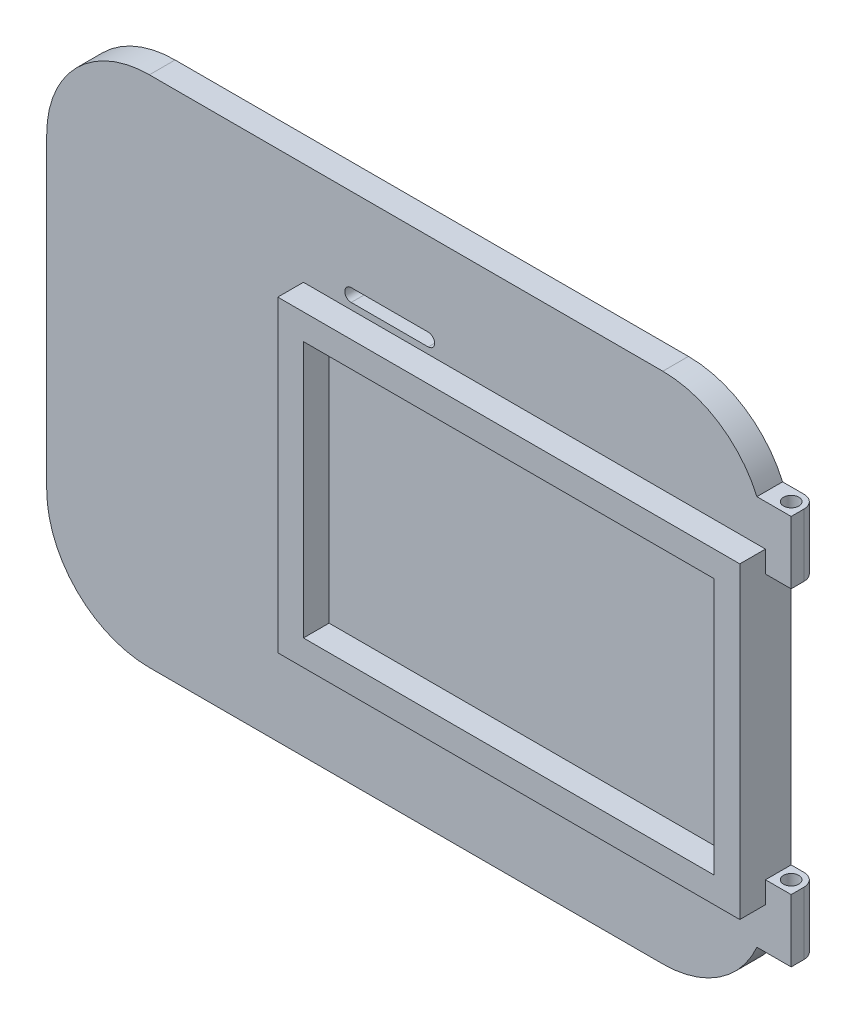
SolidWorks part; units mm, degrees
ref_plane "Front Plane" through (0, 0, 0) normal (0, 0, 1) x (1, 0, 0)
ref_plane "Top Plane" through (0, 0, 0) normal (0, 1, 0) x (1, 0, 0)
ref_plane "Right Plane" through (0, 0, 0) normal (1, 0, 0) x (0, 0, -1)
sketch "Sketch1" plane through (0, 0, 0) normal (0, 0, 1) x (1, 0, 0)
  line L0 (-63.5, 63.5) -> (63.5, 63.5)
  line L1 (63.5, -63.5) -> (-63.5, -63.5)
  line L2 (-88.9, -38.1) -> (-88.9, 38.1)
  line L3 (88.9, -38.1) -> (88.9, 38.1)
  arc A0 (-88.9, 38.1) -> (-63.5, 63.5) centre (-63.5, 38.1) cw
  arc A1 (-63.5, -63.5) -> (-88.9, -38.1) centre (-63.5, -38.1) cw
  arc A2 (63.5, -63.5) -> (88.9, -38.1) centre (63.5, -38.1) ccw
  arc A3 (88.9, 38.1) -> (63.5, 63.5) centre (63.5, 38.1) ccw
  dimension "D1" = 25.4
  dimension "D2" = 88.9
  dimension "D3" = 88.9
  dimension "D4" = 63.5
  dimension "D5" = 63.5
extrude "Boss-Extrude1" add sketch "Sketch1" against normal blind 6.35
sketch "Sketch3" plane through (0, 0, 0) normal (0, 0, 1) x (1, 0, 0)
  line L0 (63.5, 63.5) -> (88.9, 63.5) construction
  line L1 (88.9, 63.5) -> (95.25, 63.5) construction
  line L6 (95.25, 32.75) -> (95.25, 48.26)
  line L8 (95.25, 48.26) -> (86.7795, 48.26)
  line L9 (95.25, 63.5) -> (95.25, 32.75) construction
  line L10 (95.25, 32.75) -> (88.9, 32.75)
  line L11 (88.9, -38.1) -> (88.9, 38.1) construction
  line L12 (88.9, 32.75) -> (88.9, 38.1)
  arc A0 (88.9, 38.1) -> (86.7795, 48.26) centre (63.5, 38.1) ccw
  dimension "D5" = 25.4
  dimension "D1" = 25.4
  dimension "D2" = 6.35
  dimension "D3" = 30.75
  dimension "D4" = 15.24
extrude "Boss-Extrude2" add sketch "Sketch3" against normal up to surface (6.35 mm away) up to face at (0, 0, -6.35)
sketch "Sketch4" plane through (0, 48.26, 0) normal (0, 1, 0) x (1, 0, 0)
  line L0 (95.25, 3.175) -> (92.075, 3.175) construction
  line L1 (95.25, 6.35) -> (95.25, 0) construction
  circle A0 centre (92.075, 3.175) radius 1.905
  point P6 (93.98, 3.175)
  dimension "D1" = 3.81
  dimension "D2" = 1.27
extrude "Cut-Extrude2" cut sketch "Sketch4" against normal up to next
sketch "Sketch5" plane through (0, 0, 0) normal (0, 0, 1) x (1, 0, 0)
  line L0 (0, 0) -> (88.9402, 0)
mirror "Mirror1" about plane through (0, 0, 0) normal (0, 1, 0) of "Cut-Extrude2", "Boss-Extrude2"
sketch "Sketch7" plane through (0, 0, -6.35) normal (0, 0, -1) x (-1, 0, 0)
  line L0 (0, 0) -> (57.15, 0) construction
  point P4 (57.15, 0)
  dimension "D1" = 57.15
ref_plane "Plane1" through (-57.15, 0, -6.35) normal (-1, 0, 0) x (0, 0, 1)
sketch "Sketch8" plane through (-57.15, 0, -6.35) normal (-1, 0, 0) x (0, 0, 1)
  line L0 (0, 0) -> (0, 38.1) construction
  line L1 (0, 38.1) -> (0, 44.45)
  line L2 (-19.05, 25.4) -> (-19.05, -25.4)
  line L3 (0, 24.7494) -> (-24.0575, 24.7494) construction
  line L4 (-12.7, 25.4) -> (-12.7, 40.5526) construction
  line L5 (-19.05, 0) -> (-12.7, 0) construction
  line L6 (-12.7, -25.4) -> (-12.7, 25.4)
  line L7 (0, -38.1) -> (0, -44.45)
  arc A0 (0, 44.45) -> (-19.05, 25.4) centre (0, 25.4) ccw
  arc A1 (0, 38.1) -> (-12.7, 25.4) centre (0, 25.4) ccw
  arc A2 (0, -38.1) -> (-12.7, -25.4) centre (0, -25.4) cw
  arc A3 (0, -44.45) -> (-19.05, -25.4) centre (0, -25.4) cw
  dimension "D1" = 38.1
  dimension "D2" = 6.35
  dimension "D3" = 19.7006
  dimension "D4" = 12.7
extrude "Boss-Extrude3" add sketch "Sketch8" against normal blind 12.7
fillet "Fillet1" radius 6.35 1 edges at (-50.8, -44.45, -6.35)
fillet "Fillet2" radius 6.35 1 edges at (-57.15, -44.0467, -6.35)
fillet "Fillet3" radius 6.35 1 edges at (-44.45, -44.0467, -6.35)
fillet "Fillet4" radius 6.35 3 edges at (-50.8, 44.45, -6.35) (-44.45, 41.275, -6.35) (-57.15, 41.275, -6.35)
fillet "Fillet5" radius 3.175 2 edges at (95.25, -40.505, -6.35) (95.25, 40.505, -6.35)
sketch "Sketch9" plane through (0, 0, 0) normal (0, 0, 1) x (1, 0, 0)
  line L0 (88.9402, 0) -> (-88.9, 0) construction
  line L1 (-88.9, 38.1) -> (-88.9, -38.1) construction
  line L22 (82.55, 31.75) -> (-19.05, 31.75)
  line L23 (82.55, 31.75) -> (82.55, -31.75)
  line L24 (82.55, -31.75) -> (-19.05, -31.75)
  line L25 (-19.05, 31.75) -> (-19.05, -31.75)
  line L26 (-63.5, -63.5) -> (63.5, -63.5) construction
  line L27 (88.9, -32.75) -> (88.9, 32.75) construction
  line L28 (88.9, 38.1) -> (88.9, -38.1)
  line L29 (88.9, -38.1) -> (-25.4, -38.1)
  line L30 (-25.4, 38.1) -> (-25.4, -38.1)
  line L31 (88.9, 38.1) -> (-25.4, 38.1)
  dimension "D1" = 63.5
  dimension "D2" = 101.6
  dimension "D3" = 31.75
  dimension "D4" = 6.35
  dimension "D5" = 6.35
extrude "Boss-Extrude4" add sketch "Sketch9" along normal blind 6.35
sketch "Sketch10" plane through (0, 0, 0) normal (0, 0, 1) x (1, 0, 0)
  line L0 (-19.05, 31.75) -> (-19.05, 41.275) construction
  line L2 (-13.589, 41.275) -> (5.461, 41.275) construction
  line L3 (-13.589, 42.8625) -> (5.461, 42.8625)
  line L4 (-13.589, 39.6875) -> (5.461, 39.6875)
  line L5 (-19.05, 41.275) -> (-4.064, 41.275) construction
  arc A0 (-13.589, 42.8625) -> (-13.589, 39.6875) centre (-13.589, 41.275) ccw
  arc A1 (5.461, 39.6875) -> (5.461, 42.8625) centre (5.461, 41.275) ccw
  point P1 (0, 0)
  point P6 (-4.064, 41.275)
  dimension "D1" = 9.525
  dimension "D3" = 19.05
  dimension "D4" = 3.175
  dimension "D5" = 14.986
extrude "Cut-Extrude3" cut sketch "Sketch10" against normal up to next
